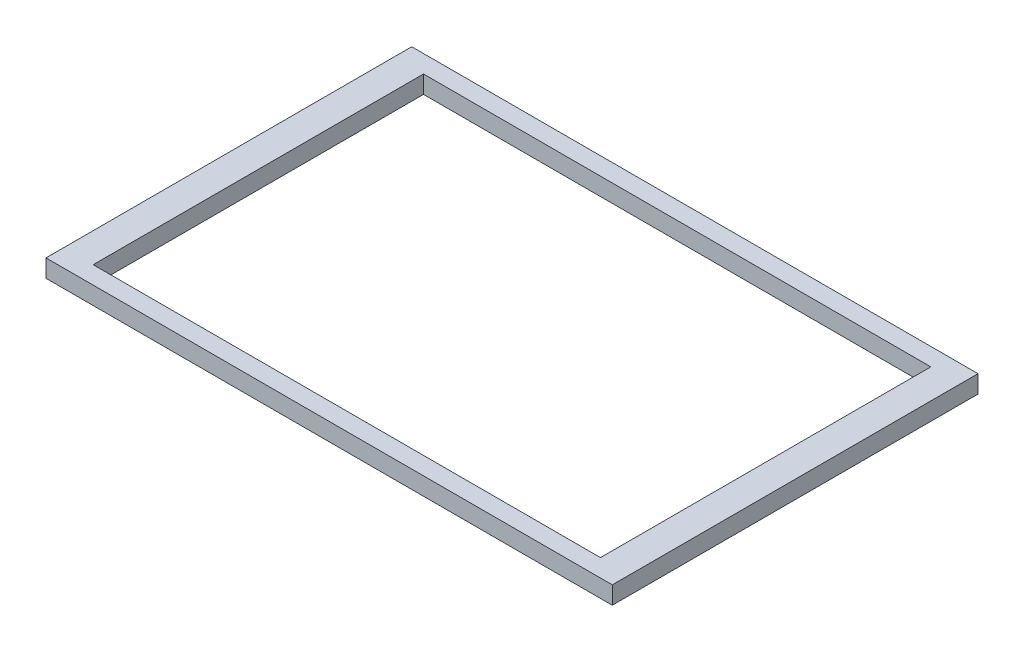
SolidWorks part; units mm, degrees
ref_plane "Front" through (0, 0, 0) normal (0, 0, 1) x (1, 0, 0)
ref_plane "Top" through (0, 0, 0) normal (0, 1, 0) x (1, 0, 0)
ref_plane "Right" through (0, 0, 0) normal (1, 0, 0) x (0, 0, -1)
sketch "Sketch1" plane through (0, 0, 0) normal (0, 1, 0) x (1, 0, 0)
  line L1 (-43, -28) -> (43, -28)
  line L2 (-43, -28) -> (-43, 28)
  line L3 (-43, 28) -> (43, 28)
  line L4 (43, -28) -> (43, 28)
  line L5 (-43, -28) -> (43, 28) construction
  line L6 (-43, 28) -> (43, -28) construction
  line L7 (-48, -31) -> (48, -31)
  line L8 (-48, -31) -> (-48, 31)
  line L9 (-48, 31) -> (48, 31)
  line L10 (48, -31) -> (48, 31)
  line L11 (-48, -31) -> (48, 31) construction
  line L12 (-48, 31) -> (48, -31) construction
  point P0 (0, 0)
  point P6 (0, 0)
  dimension "D1" = 86
  dimension "D2" = 56
  dimension "D3" = 3
  dimension "D4" = 5
extrude "Boss-Extrude1" add sketch "Sketch1" along normal blind 3
sketch "Sketch4" plane through (0, 0, 0) normal (1, 0, 0) x (0, 0, -1)
  line L0 (39.1947, 1.3012) -> (-67.9431, 60.6887) construction
  line L1 (39.1947, 1.3012) -> (-67.9431, 60.6887) construction
  line L2 (27.8171, -5.4986) -> (48.4056, 6.3882) construction
  line L3 (27.8171, -5.4986) -> (48.4056, 6.3882) construction
  line L4 (39.1947, 1.3012) -> (41.3326, 123.7791) construction
  line L5 (39.1947, 1.3012) -> (41.3326, 123.7791) construction
sketch "Sketch7" plane through (0, 0, 0) normal (1, 0, 0) x (0, 0, -1)
  line L13 (52.4678, 3.2487) -> (51.5928, 4.7642)
  line L14 (52.4678, 3.2487) -> (51.5928, 4.7642)
  line L15 (30.8171, -21.5825) -> (30.8171, -9.2513)
  line L16 (30.8171, -9.2513) -> (32.9389, -8.0263)
  line L17 (32.9389, -8.0263) -> (31.9389, -6.2943)
  line L18 (31.9389, -6.2943) -> (49.346, 3.7557)
  line L19 (49.346, 3.7557) -> (50.346, 2.0237)
  line L20 (50.346, 2.0237) -> (52.4678, 3.2487)
  line L22 (48.4056, 6.3882) -> (27.8171, -5.4986)
  line L23 (27.8171, -5.4986) -> (27.8171, -15.8754)
  line L28 (30.8171, -21.5825) -> (30.8171, -9.2513)
  line L29 (30.8171, -9.2513) -> (32.9389, -8.0263)
  line L30 (32.9389, -8.0263) -> (31.9389, -6.2943)
  line L31 (31.9389, -6.2943) -> (49.346, 3.7557)
  line L32 (49.346, 3.7557) -> (50.346, 2.0237)
  line L33 (50.346, 2.0237) -> (52.4678, 3.2487)
  line L35 (48.4056, 6.3882) -> (27.8171, -5.4986)
  line L36 (27.8171, -5.4986) -> (27.8171, -15.8754)
  line L53 (51.5928, 4.7642) -> (48.4056, 6.3882)
  line L54 (51.5928, 4.7642) -> (48.4056, 6.3882)
  line L190 (27.8171, -19.124) -> (27.8171, -23.3146)
  line L192 (26.8171, -19.124) -> (27.8171, -19.124)
  line L193 (26.8171, -19.124) -> (27.8171, -19.124)
  line L273 (27.8171, -19.124) -> (27.8171, -23.3146)
  line L275 (27.8171, -23.3146) -> (30.8171, -21.5825)
  line L285 (27.8171, -23.3146) -> (30.8171, -21.5825)
  line L287 (27.8171, -18.5466) -> (26.8171, -19.124)
  line L289 (27.8171, -18.5466) -> (26.8171, -19.124)
  line L352 (27.8171, -17.8486) -> (27.8171, -18.5466)
  line L353 (27.8171, -17.8486) -> (27.8171, -18.5466)
  line L354 (27.8171, -15.8754) -> (28.85, -15.8754)
  line L355 (27.8171, -15.8754) -> (28.85, -15.8754)
  line L356 (28.85, -15.8754) -> (28.85, -17.8486)
  line L357 (28.85, -15.8754) -> (28.85, -17.8486)
  line L358 (28.85, -17.8486) -> (27.8171, -17.8486)
  line L359 (28.85, -17.8486) -> (27.8171, -17.8486)
  dimension "D1" = 0
